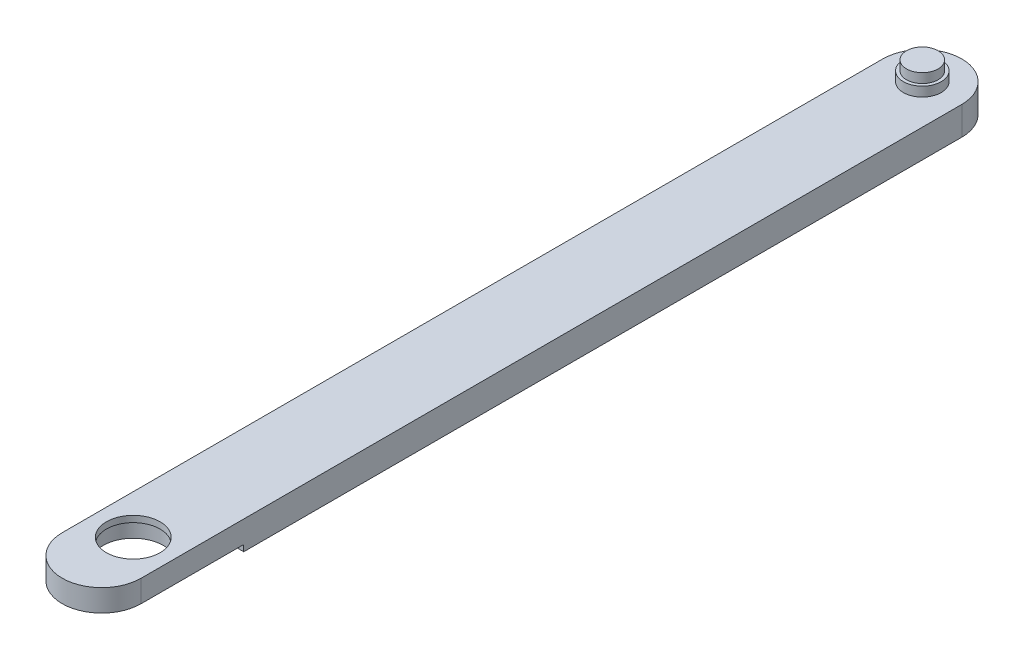
SolidWorks part; units mm, degrees
material "7075-T6 (SN)"
ref_plane "정면" through (0, 0, 0) normal (0, 0, 1) x (1, 0, 0)
ref_plane "윗면" through (0, 0, 0) normal (0, 1, 0) x (1, 0, 0)
ref_plane "우측면" through (0, 0, 0) normal (1, 0, 0) x (0, 0, -1)
sketch "스케치1" plane through (0, 0, 0) normal (0, 1, 0) x (1, 0, 0)
  circle A0 centre (0, 0) radius 5
  dimension "D1" = 10
extrude "보스-돌출1" add sketch "스케치1" along normal blind 10.5 and the other way blind 10.5
sketch "스케치6" plane through (0, 0, 0) normal (0, 1, 0) x (1, 0, 0)
  line L0 (-12.5, 0) -> (-12.5, -260)
  line L1 (0, 0) -> (0, -260) construction
  line L2 (12.5, 0) -> (12.5, -260)
  arc A0 (12.5, 0) -> (-12.5, 0) centre (0, 0) ccw
  arc A1 (-12.5, -260) -> (12.5, -260) centre (0, -260) ccw
  dimension "D1" = 25
  dimension "D3" = 25
  dimension "D2" = 260
extrude "보스-돌출3" add sketch "스케치6" along normal blind 4.5 and the other way blind 4.5
sketch "스케치7" plane through (0, -4.5, 0) normal (0, -1, 0) x (1, 0, 0)
  circle A0 centre (0, 0) radius 6
  dimension "D1" = 12
extrude "보스-돌출4" add sketch "스케치7" along normal blind 3
sketch "스케치8" plane through (0, 4.5, 0) normal (0, 1, 0) x (1, 0, 0)
  circle A0 centre (0, 0) radius 6
  dimension "D1" = 12
extrude "보스-돌출5" add sketch "스케치8" along normal blind 3
sketch "스케치9" plane through (0, -4.5, 0) normal (0, -1, 0) x (1, 0, 0)
  circle A0 centre (0, 250) radius 9.5
  dimension "D1" = 19
  dimension "D2" = 250
extrude "컷-돌출1" cut sketch "스케치9" against normal blind 7
sketch "스케치10" plane through (0, 2.5, 0) normal (0, -1, 0) x (1, 0, 0)
  circle A0 centre (0, 250) radius 8.5
  dimension "D1" = 17
  dimension "D2" = 250
extrude "컷-돌출2" cut sketch "스케치10" against normal through all
sketch "스케치13" plane through (0, -4.5, 0) normal (0, -1, 0) x (1, 0, 0)
  line L0 (-12.5, 0) -> (-12.5, 260) construction
  line L5 (-12.5, 227.5) -> (12.5, 227.5)
  line L6 (-12.5, 227.5) -> (-12.5, 272.5)
  line L7 (-12.5, 272.5) -> (12.5, 272.5)
  line L8 (12.5, 227.5) -> (12.5, 272.5)
  arc A0 (12.5, 260) -> (-12.5, 260) centre (0, 260) ccw construction
  point P0 (0, 250)
  dimension "D1" = 45
extrude "컷-돌출3" cut sketch "스케치13" against normal blind 2
